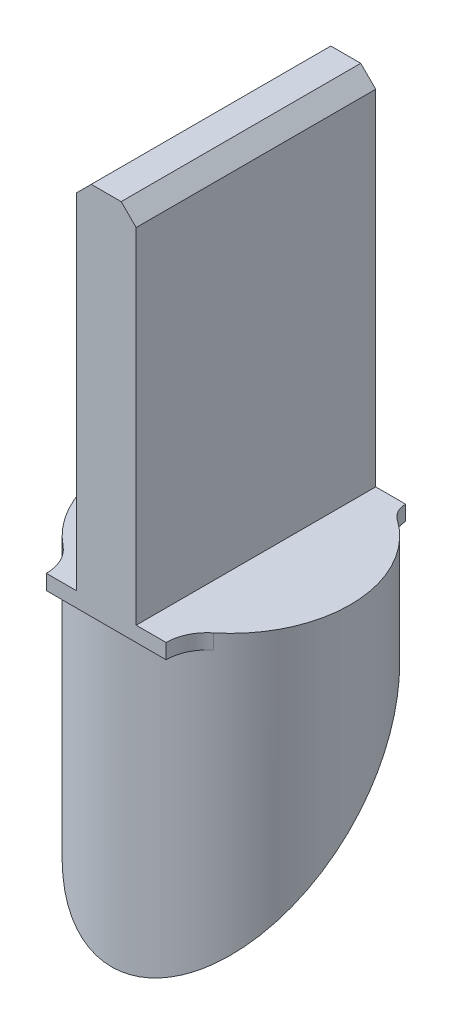
SolidWorks part; units mm, degrees
ref_plane "Front Plane" through (0, 0, 0) normal (0, 0, 1) x (1, 0, 0)
ref_plane "Top Plane" through (0, 0, 0) normal (0, 1, 0) x (1, 0, 0)
ref_plane "Right Plane" through (0, 0, 0) normal (1, 0, 0) x (0, 0, -1)
sketch "Sketch2" plane through (0, 0, 0) normal (1, 0, 0) x (0, 0, -1)
  line L0 (1.0414, 1055.2611) -> (1.0414, 991.9416) construction
  line L1 (1.0414, 1055.2611) -> (-24.2683, 1055.2611)
  line L2 (-24.2683, 1055.2611) -> (-24.2683, 991.9416)
  line L3 (-24.2683, 991.9416) -> (1.0414, 991.9416)
  line L4 (1.0414, 1055.2611) -> (1.0414, 991.9416)
revolve "Revolve1" add sketch "Sketch2" angle 360 about L0
sketch "Sketch3" plane through (0, 0, 0) normal (1, 0, 0) x (0, 0, -1)
  line L0 (-24.2683, 991.9416) -> (26.3511, 1042.5611)
  line L1 (26.3511, 1042.5611) -> (26.3511, 991.9416)
  line L2 (26.3511, 991.9416) -> (-24.2683, 991.9416)
extrude "Cut-Extrude1" cut sketch "Sketch3" against normal through all both and the other way through all
shell "Shell1" thickness 3.175 removed face at (0, 1042.5611, -26.3511)
sketch "Sketch4" plane through (0, 1055.2611, 0) normal (0, 1, 0) x (1, 0, 0)
  line L12 (12.7, -25.4) -> (12.7, 25.4) construction
  line L13 (12.7, -25.4) -> (-12.7, -25.4)
  line L14 (-12.7, -25.4) -> (-12.7, 25.4) construction
  line L15 (12.7, 25.4) -> (-12.7, 25.4)
  line L16 (12.7, -25.4) -> (-12.7, 25.4) construction
  line L17 (-12.7, -25.4) -> (12.7, 25.4) construction
  arc A0 (12.7, 25.4) -> (14.6115, 21.7075) centre (17.2222, 25.4) ccw
  circle A1 centre (0, 1.0414) radius 25.3097
  arc A2 (-14.6115, 21.7075) -> (-15.9306, -18.6258) centre (0, 1.0414) ccw
  arc A3 (15.9306, -18.6258) -> (12.7, -25.4) centre (21.4176, -25.4) ccw
  arc A4 (-12.7, -25.4) -> (-15.9306, -18.6258) centre (-21.4176, -25.4) ccw
  arc A5 (-12.7, 25.4) -> (-14.6115, 21.7075) centre (-17.2222, 25.4) cw
  arc A6 (15.9306, -18.6258) -> (14.6115, 21.7075) centre (0, 1.0414) ccw
  point P0 (0, 0)
  dimension "D1" = 25.4
  dimension "D2" = 50.8
  dimension "D3" = 0
extrude "Boss-Extrude1" add sketch "Sketch4" along normal blind 3.175
sketch "Sketch5" plane through (0, 1058.4361, 0) normal (0, 1, 0) x (1, 0, 0)
  line L1 (6.35, -25.4) -> (6.35, 25.4)
  line L2 (6.35, -25.4) -> (-6.35, -25.4)
  line L3 (-6.35, -25.4) -> (-6.35, 25.4)
  line L4 (6.35, 25.4) -> (-6.35, 25.4)
  line L5 (-6.35, 0) -> (6.35, 0) construction
  line L6 (0, -25.4) -> (0, 25.4) construction
  line L7 (12.7, 25.4) -> (-12.7, 25.4) construction
  point P0 (0, 0)
  dimension "D1" = 12.7
extrude "Boss-Extrude2" add sketch "Sketch5" along normal blind 76.2
chamfer "Chamfer1" distance 3.175 angle 45 2 edges at (6.35, 1134.6361, 0) (-6.35, 1134.6361, 0)
sketch "Sketch6" plane through (0, 1134.6361, 0) normal (0, 1, 0) x (1, 0, 0)
  line L0 (0, -22.225) -> (0, 22.225) construction
  point P4 (0, 0)
  dimension "D1" = 44.45
sketch "Sketch7" plane through (0, 1055.2611, 0) normal (0, -1, 0) x (1, 0, 0)
  line L0 (0, 22.225) -> (0, -22.225) construction
  line L1 (0, 22.225) -> (0, -22.225) construction
